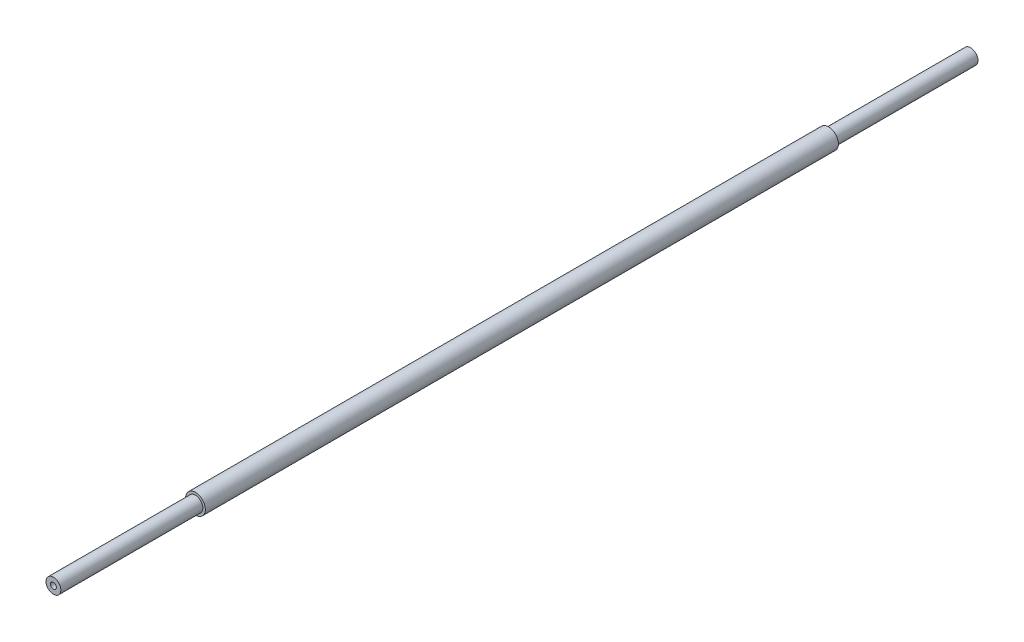
SolidWorks part; units mm, degrees
ref_plane "Front Plane" through (0, 0, 0) normal (0, 0, 1) x (1, 0, 0)
ref_plane "Top Plane" through (0, 0, 0) normal (0, 1, 0) x (1, 0, 0)
ref_plane "Right Plane" through (0, 0, 0) normal (1, 0, 0) x (0, 0, -1)
sketch "Sketch1" plane through (0, 0, 0) normal (0, 0, 1) x (1, 0, 0)
  circle A0 centre (0, 0) radius 4.7625
  circle A1 centre (0, 0) radius 6.35
  dimension "D1" = 9.525
  dimension "D2" = 12.7
extrude "Boss-Extrude1" add sketch "Sketch1" along normal blind 588.772 contours A0 region at (0, 0, 0)
extrude "Boss-Extrude2" add sketch "Sketch1<3>" along normal blind 406.4 from offset 91.186
sketch "Sketch1<3>" plane through (0, 0, 0) normal (0, 0, 1) x (1, 0, 0) same geometry as "Sketch1"
hole_wizard "#25 (0.1495) Diameter Hole1" positions "Sketch3" profile "Sketch2" hole size "#25" standard "ANSI Inch" end condition through all
sketch "Sketch3" plane through (0, 0, 588.772) normal (0, 0, 1) x (1, 0, 0)
  point P0 (0, 0)
sketch "Sketch2" plane through (0, 0, 588.772) normal (1, 0, 0) x (0, -1, 0)
  line L0 (0, 0) -> (0, 588.772)
  line L1 (0, 588.772) -> (1.8986, 588.772)
  line L2 (1.8986, 588.772) -> (1.8986, 0)
  line L5 (1.8986, 0) -> (0, 0)
  line L11 (0, -6.35) -> (0, 107.95) construction
  dimension "Thru Hole Dia." = 3.7973
  dimension "Thru Hole Depth" = 588.772
